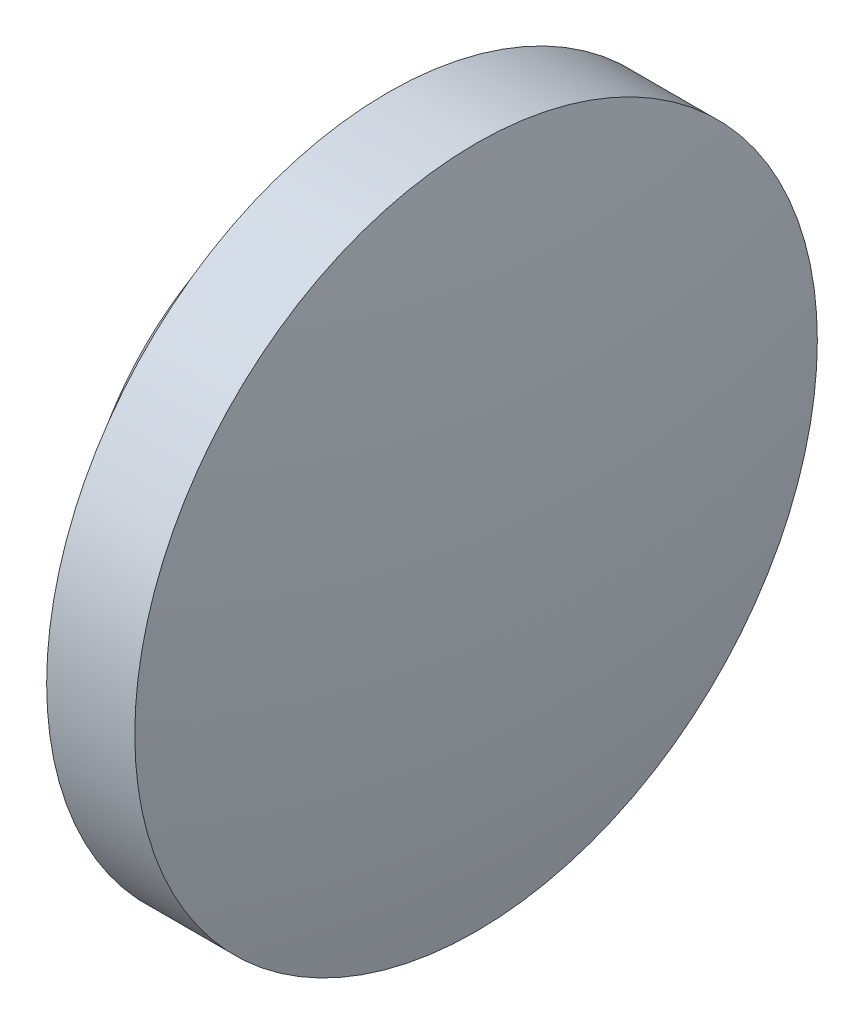
SolidWorks part; units mm, degrees
material "Glass"
ref_plane "Front Plane" through (0, 0, 0) normal (0, 0, 1) x (1, 0, 0)
ref_plane "Top Plane" through (0, 0, 0) normal (0, 1, 0) x (1, 0, 0)
ref_plane "Right Plane" through (0, 0, 0) normal (1, 0, 0) x (0, 0, -1)
sketch "Sketch1" plane through (0, 0, 0) normal (0, 0, 1) x (1, 0, 0)
  line L0 (0, 0) -> (-97.9139, 0) construction
  line L1 (-2.655, 7.5) -> (-0.7186, 7.5)
  line L2 (-6.38, 0) -> (0, 0)
  arc A0 (-0.7186, 7.5) -> (0, 0) centre (-39.5, 0) cw
  spline S0 degree 3 poles (-2.655, 7.5) (-3.0041, 6.9935) (-3.6073, 6.1611) (-4.4604, 5.0156) (-5.1284, 4.0265) (-5.6832, 3.0299) (-6.2083, 1.7111) (-6.383, 0.6787) (-6.38, 0) knots 0 0 0 0 0.216367 0.361524 0.502322 0.635901 0.761914 1 1 1 1
  point P0 (-6.38, 0)
  point P7 (-6.302, 1)
  point P8 (-6.065, 2)
  point P9 (-5.671, 3)
  point P10 (-5.125, 4)
  point P11 (-4.46, 5)
  point P12 (-3.73, 6)
  point P13 (-3.005, 7)
  dimension "D1" = 7.5
  dimension "D2" = 39.5
  dimension "D3" = 6.38
  dimension "D4" = 0.078
  dimension "D5" = 1
  dimension "D6" = 2
  dimension "D7" = 3
  dimension "D8" = 4
  dimension "D9" = 5
  dimension "D10" = 6
  dimension "D11" = 7
  dimension "D12" = 3.725
  dimension "D13" = 0.315
  dimension "D14" = 0.709
  dimension "D15" = 1.255
  dimension "D16" = 1.92
  dimension "D17" = 2.65
  dimension "D18" = 3.375
revolve "Revolve1" add sketch "Sketch1" angle 360 about L0
sketch3d "3DSketch1"
  circle A0 centre (-0.7186, 0, 0) radius 7.5 construction
  point P2 (6.7814, 0, 0)
